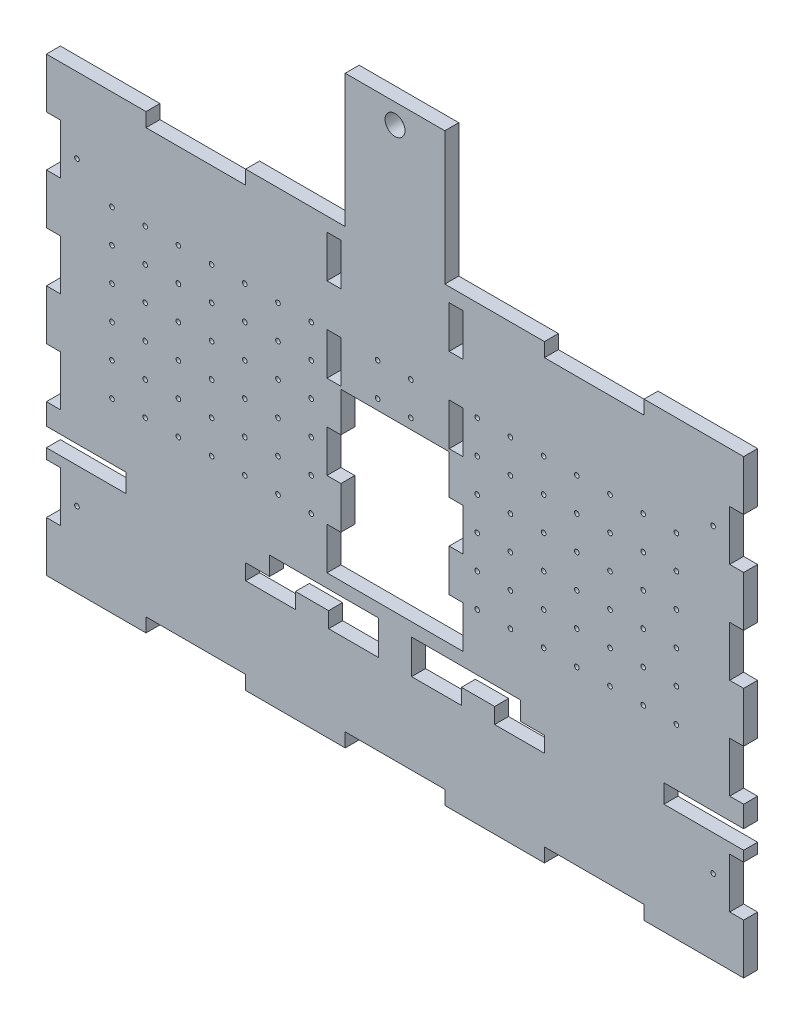
SolidWorks part; units mm, degrees
ref_plane "Front Plane" through (0, 0, 0) normal (0, 0, 1) x (1, 0, 0)
ref_plane "Top Plane" through (0, 0, 0) normal (0, 1, 0) x (1, 0, 0)
ref_plane "Right Plane" through (0, 0, 0) normal (1, 0, 0) x (0, 0, -1)
sketch "Sketch1" plane through (0, 0, 0) normal (0, 0, 1) x (1, 0, 0)
  line L1 (-127.8759, 88.4641) -> (138.8241, 88.4641)
  line L2 (-127.8759, 88.4641) -> (-127.8759, -84.2559)
  line L3 (-127.8759, -84.2559) -> (138.8241, -84.2559)
  line L4 (138.8241, 88.4641) -> (138.8241, -84.2559)
  dimension "D1" = 266.7
  dimension "D2" = 172.72
extrude "Boss-Extrude1" add sketch "Sketch1" along normal blind 5.334
sketch "Sketch2" plane through (0, 0, 5.334) normal (0, 0, 1) x (1, 0, 0)
  line L0 (-127.8759, -84.2559) -> (138.8241, -84.2559) construction
  line L1 (-89.7759, -84.2559) -> (-51.6759, -84.2559)
  line L2 (-89.7759, -84.2559) -> (-89.7759, -78.9219)
  line L3 (-89.7759, -78.9219) -> (-51.6759, -78.9219)
  line L4 (-51.6759, -84.2559) -> (-51.6759, -78.9219)
  line L5 (-89.7759, -78.9219) -> (-127.8759, -78.9219) construction
  line L6 (-13.5759, -84.2559) -> (24.5241, -84.2559)
  line L7 (-13.5759, -84.2559) -> (-13.5759, -78.9219)
  line L8 (-13.5759, -78.9219) -> (24.5241, -78.9219)
  line L9 (24.5241, -84.2559) -> (24.5241, -78.9219)
  line L10 (62.6241, -84.2559) -> (100.7241, -84.2559)
  line L11 (62.6241, -84.2559) -> (62.6241, -78.9219)
  line L12 (62.6241, -78.9219) -> (100.7241, -78.9219)
  line L13 (100.7241, -84.2559) -> (100.7241, -78.9219)
  line L14 (-127.8759, 88.4641) -> (-127.8759, -84.2559) construction
  line L15 (-51.6759, -78.9219) -> (-13.5759, -78.9219) construction
  line L16 (24.5241, -78.9219) -> (62.6241, -78.9219) construction
  line L17 (62.6241, -78.9219) -> (62.364, -79.7896) construction
  line L18 (100.7241, -78.9219) -> (138.8241, -78.9219) construction
  line L19 (138.8241, -84.2559) -> (138.8241, 88.4641) construction
  line L20 (-127.8759, 2.1041) -> (138.8241, 2.1041) construction
  line L21 (100.7241, 88.4641) -> (100.7241, 83.1301)
  line L22 (62.6241, 83.1301) -> (100.7241, 83.1301)
  line L23 (62.6241, 88.4641) -> (62.6241, 83.1301)
  line L24 (24.5241, 88.4641) -> (24.5241, 83.1301)
  line L25 (-13.5759, 83.1301) -> (24.5241, 83.1301)
  line L26 (-13.5759, 88.4641) -> (-13.5759, 83.1301)
  line L27 (-51.6759, 88.4641) -> (-51.6759, 83.1301)
  line L28 (-89.7759, 83.1301) -> (-51.6759, 83.1301)
  line L29 (-89.7759, 88.4641) -> (-89.7759, 83.1301)
  line L30 (62.6241, 88.4641) -> (100.7241, 88.4641)
  line L31 (-13.5759, 88.4641) -> (24.5241, 88.4641)
  line L32 (-89.7759, 88.4641) -> (-51.6759, 88.4641)
  dimension "D1" = 5.334
extrude "Cut-Extrude1" cut sketch "Sketch2" against normal through all
sketch "Sketch5" plane through (0, 0, 5.334) normal (0, 0, 1) x (1, 0, 0)
  line L0 (5.4741, 83.1301) -> (5.4741, -78.9219) construction
  line L1 (-13.5759, 83.1301) -> (24.5241, 83.1301) construction
  line L2 (24.5241, -78.9219) -> (-13.5759, -78.9219) construction
  line L3 (11.8241, -34.8224) -> (11.8241, -41.9344)
  line L4 (-42.5319, -34.8224) -> (-0.8759, -34.8224)
  line L5 (-42.5319, -34.8224) -> (-42.5319, -41.9344)
  line L6 (-42.5319, -41.9344) -> (-0.8759, -41.9344)
  line L7 (-0.8759, -34.8224) -> (-0.8759, -41.9344)
  line L8 (53.4801, -41.9344) -> (11.8241, -41.9344)
  line L9 (53.4801, -34.8224) -> (53.4801, -41.9344)
  line L10 (53.4801, -34.8224) -> (11.8241, -34.8224)
  line L11 (11.8241, -34.8224) -> (-0.8759, -34.8224) construction
  line L12 (-0.8759, -41.9344) -> (11.8241, -41.9344) construction
  line L13 (-139.0519, -34.8224) -> (-97.3959, -34.8224)
  line L14 (-139.0519, -34.8224) -> (-139.0519, -41.9344)
  line L15 (-139.0519, -41.9344) -> (-97.3959, -41.9344)
  line L16 (-97.3959, -34.8224) -> (-97.3959, -41.9344)
  line L18 (108.3441, -34.8224) -> (108.3441, -41.9344)
  line L19 (150.0001, -41.9344) -> (108.3441, -41.9344)
  line L20 (150.0001, -34.8224) -> (150.0001, -41.9344)
  line L21 (150.0001, -34.8224) -> (108.3441, -34.8224)
  dimension "D2" = 41.656
  dimension "D3" = 6.35
  dimension "D1" = 7.112
  dimension "D4" = 2
extrude "Cut-Extrude3" cut sketch "Sketch5" against normal through all
sketch "Sketch9" plane through (0, 0, 5.334) normal (0, 0, 1) x (1, 0, 0)
  line L0 (-127.8759, 88.4641) -> (-127.8759, -34.8224) construction
  line L1 (-127.8759, -65.0647) -> (-122.5419, -65.0647)
  line L2 (-127.8759, -65.0647) -> (-127.8759, -45.8736)
  line L3 (-127.8759, -45.8736) -> (-122.5419, -45.8736)
  line L4 (-122.5419, -65.0647) -> (-122.5419, -45.8736)
  line L5 (-122.5419, 69.273) -> (-122.5419, 88.4641) construction
  line L6 (-127.8759, -26.6825) -> (-122.5419, -26.6825)
  line L7 (-127.8759, -26.6825) -> (-127.8759, -7.4914)
  line L8 (-127.8759, -7.4914) -> (-122.5419, -7.4914)
  line L9 (-122.5419, -26.6825) -> (-122.5419, -7.4914)
  line L10 (-127.8759, 11.6997) -> (-122.5419, 11.6997)
  line L11 (-127.8759, 11.6997) -> (-127.8759, 30.8908)
  line L12 (-127.8759, 30.8908) -> (-122.5419, 30.8908)
  line L13 (-122.5419, 11.6997) -> (-122.5419, 30.8908)
  line L14 (-127.8759, 50.0819) -> (-122.5419, 50.0819)
  line L15 (-127.8759, 50.0819) -> (-127.8759, 69.273)
  line L16 (-127.8759, 69.273) -> (-122.5419, 69.273)
  line L17 (-122.5419, 50.0819) -> (-122.5419, 69.273)
  line L18 (-89.7759, 88.4641) -> (-127.8759, 88.4641) construction
  line L19 (-122.5419, 50.0819) -> (-122.5419, 30.8908) construction
  line L20 (-122.5419, 11.6997) -> (-122.5419, -7.4914) construction
  line L21 (-122.5419, -26.6825) -> (-122.5419, -45.8736) construction
  line L22 (-122.5419, -65.0647) -> (-122.5419, -84.2559) construction
  line L23 (-127.8759, -84.2559) -> (-89.7759, -84.2559) construction
  line L24 (5.4741, 83.1301) -> (5.4741, -78.9219) construction
  line L25 (-13.5759, 83.1301) -> (24.5241, 83.1301) construction
  line L26 (24.5241, -78.9219) -> (-13.5759, -78.9219) construction
  line L27 (133.4901, -65.0647) -> (133.4901, -84.2559) construction
  line L28 (133.4901, -26.6825) -> (133.4901, -45.8736) construction
  line L29 (133.4901, 11.6997) -> (133.4901, -7.4914) construction
  line L30 (133.4901, 50.0819) -> (133.4901, 30.8908) construction
  line L31 (133.4901, 69.273) -> (133.4901, 88.4641) construction
  line L32 (133.4901, 50.0819) -> (133.4901, 69.273)
  line L33 (138.8241, 69.273) -> (133.4901, 69.273)
  line L34 (138.8241, 50.0819) -> (138.8241, 69.273)
  line L35 (138.8241, 50.0819) -> (133.4901, 50.0819)
  line L36 (133.4901, 11.6997) -> (133.4901, 30.8908)
  line L37 (138.8241, 30.8908) -> (133.4901, 30.8908)
  line L38 (138.8241, 11.6997) -> (138.8241, 30.8908)
  line L39 (138.8241, 11.6997) -> (133.4901, 11.6997)
  line L40 (133.4901, -26.6825) -> (133.4901, -7.4914)
  line L41 (138.8241, -7.4914) -> (133.4901, -7.4914)
  line L42 (138.8241, -26.6825) -> (138.8241, -7.4914)
  line L43 (138.8241, -26.6825) -> (133.4901, -26.6825)
  line L44 (133.4901, -65.0647) -> (133.4901, -45.8736)
  line L45 (138.8241, -45.8736) -> (133.4901, -45.8736)
  line L46 (138.8241, -65.0647) -> (138.8241, -45.8736)
  line L47 (138.8241, -65.0647) -> (133.4901, -65.0647)
  dimension "D1" = 5.334
extrude "Cut-Extrude7" cut sketch "Sketch9" against normal through all
sketch "Sketch10" plane through (0, 88.4641, 0) normal (0, 1, 0) x (1, 0, 0)
  line L1 (24.5241, -5.334) -> (62.6241, -5.334)
  line L2 (24.5241, -5.334) -> (24.5241, 0)
  line L3 (24.5241, 0) -> (62.6241, 0)
  line L4 (62.6241, -5.334) -> (62.6241, 0)
extrude "Boss-Extrude2" add sketch "Sketch10" along normal blind 50.8
sketch "Sketch11" plane through (0, 0, 0) normal (0, 0, -1) x (-1, 0, 0)
  line L0 (-24.5241, 83.1301) -> (-24.5241, 139.2641) construction
  line L1 (-24.5241, 88.4641) -> (-31.1281, 88.4641)
  line L2 (-24.5241, 88.4641) -> (-24.5241, 129.1041)
  line L3 (-24.5241, 129.1041) -> (-31.1281, 129.1041)
  line L4 (-31.1281, 88.4641) -> (-31.1281, 129.1041)
  line L5 (13.5759, 88.4641) -> (51.6759, 88.4641) construction
  dimension "D1" = 6.604
  dimension "D3" = 0
extrude "Cut-Extrude8" cut sketch "Sketch11" against normal through all
sketch "Sketch12" plane through (0, 0, 5.334) normal (0, 0, 1) x (1, 0, 0)
  line L0 (62.6241, 139.2641) -> (62.6241, 83.1301) construction
  circle A0 centre (43.5741, 130.4765) radius 3.81
  dimension "D1" = 19.05
extrude "Cut-Extrude9" cut sketch "Sketch12" against normal through all
sketch "Sketch14" plane through (0, 0, 5.334) normal (0, 0, 1) x (1, 0, 0)
  line L0 (-89.7759, 88.4641) -> (-127.8759, 88.4641) construction
  circle A0 centre (-102.7976, 50.3641) radius 0.889
  circle A1 centre (-90.0976, 50.3641) radius 0.889
  circle A2 centre (-77.3976, 50.3641) radius 0.889
  circle A3 centre (-64.6976, 50.3641) radius 0.889
  circle A4 centre (-51.9976, 50.3641) radius 0.889
  circle A5 centre (-39.2976, 50.3641) radius 0.889
  circle A6 centre (-26.5976, 50.3641) radius 0.889
  circle A8 centre (-1.1976, 50.3641) radius 0.889
  circle A9 centre (11.5024, 50.3641) radius 0.889
  circle A11 centre (36.9024, 50.3641) radius 0.889
  circle A12 centre (49.6024, 50.3641) radius 0.889
  circle A13 centre (62.3024, 50.3641) radius 0.889
  circle A14 centre (75.0024, 50.3641) radius 0.889
  circle A15 centre (87.7024, 50.3641) radius 0.889
  circle A16 centre (100.4024, 50.3641) radius 0.889
  circle A17 centre (113.1024, 50.3641) radius 0.889
  circle A18 centre (-102.7976, 37.6641) radius 0.889
  circle A19 centre (-90.0976, 37.6641) radius 0.889
  circle A20 centre (-77.3976, 37.6641) radius 0.889
  circle A21 centre (-64.6976, 37.6641) radius 0.889
  circle A22 centre (-51.9976, 37.6641) radius 0.889
  circle A23 centre (-39.2976, 37.6641) radius 0.889
  circle A24 centre (-26.5976, 37.6641) radius 0.889
  circle A26 centre (-1.1976, 37.6641) radius 0.889
  circle A27 centre (11.5024, 37.6641) radius 0.889
  circle A29 centre (36.9024, 37.6641) radius 0.889
  circle A30 centre (49.6024, 37.6641) radius 0.889
  circle A31 centre (62.3024, 37.6641) radius 0.889
  circle A32 centre (75.0024, 37.6641) radius 0.889
  circle A33 centre (87.7024, 37.6641) radius 0.889
  circle A34 centre (100.4024, 37.6641) radius 0.889
  circle A35 centre (113.1024, 37.6641) radius 0.889
  circle A36 centre (-102.7976, 24.9641) radius 0.889
  circle A37 centre (-90.0976, 24.9641) radius 0.889
  circle A38 centre (-77.3976, 24.9641) radius 0.889
  circle A39 centre (-64.6976, 24.9641) radius 0.889
  circle A40 centre (-51.9976, 24.9641) radius 0.889
  circle A41 centre (-39.2976, 24.9641) radius 0.889
  circle A42 centre (-26.5976, 24.9641) radius 0.889
  circle A44 centre (-1.1976, 24.9641) radius 0.889
  circle A45 centre (11.5024, 24.9641) radius 0.889
  circle A47 centre (36.9024, 24.9641) radius 0.889
  circle A48 centre (49.6024, 24.9641) radius 0.889
  circle A49 centre (62.3024, 24.9641) radius 0.889
  circle A50 centre (75.0024, 24.9641) radius 0.889
  circle A51 centre (87.7024, 24.9641) radius 0.889
  circle A52 centre (100.4024, 24.9641) radius 0.889
  circle A53 centre (113.1024, 24.9641) radius 0.889
  circle A54 centre (-102.7976, 12.2641) radius 0.889
  circle A55 centre (-90.0976, 12.2641) radius 0.889
  circle A56 centre (-77.3976, 12.2641) radius 0.889
  circle A57 centre (-64.6976, 12.2641) radius 0.889
  circle A58 centre (-51.9976, 12.2641) radius 0.889
  circle A59 centre (-39.2976, 12.2641) radius 0.889
  circle A60 centre (-26.5976, 12.2641) radius 0.889
  circle A65 centre (36.9024, 12.2641) radius 0.889
  circle A66 centre (49.6024, 12.2641) radius 0.889
  circle A67 centre (62.3024, 12.2641) radius 0.889
  circle A68 centre (75.0024, 12.2641) radius 0.889
  circle A69 centre (87.7024, 12.2641) radius 0.889
  circle A70 centre (100.4024, 12.2641) radius 0.889
  circle A71 centre (113.1024, 12.2641) radius 0.889
  circle A72 centre (-102.7976, -0.4359) radius 0.889
  circle A73 centre (-90.0976, -0.4359) radius 0.889
  circle A74 centre (-77.3976, -0.4359) radius 0.889
  circle A75 centre (-64.6976, -0.4359) radius 0.889
  circle A76 centre (-51.9976, -0.4359) radius 0.889
  circle A77 centre (-39.2976, -0.4359) radius 0.889
  circle A78 centre (-26.5976, -0.4359) radius 0.889
  circle A79 centre (-13.8976, -0.4359) radius 0.889
  circle A80 centre (-1.1976, -0.4359) radius 0.889
  circle A81 centre (11.5024, -0.4359) radius 0.889
  circle A82 centre (24.2024, -0.4359) radius 0.889
  circle A83 centre (36.9024, -0.4359) radius 0.889
  circle A84 centre (49.6024, -0.4359) radius 0.889
  circle A85 centre (62.3024, -0.4359) radius 0.889
  circle A86 centre (75.0024, -0.4359) radius 0.889
  circle A87 centre (87.7024, -0.4359) radius 0.889
  circle A88 centre (100.4024, -0.4359) radius 0.889
  circle A89 centre (113.1024, -0.4359) radius 0.889
  circle A90 centre (-102.7976, -13.1359) radius 0.889
  circle A91 centre (-90.0976, -13.1359) radius 0.889
  circle A92 centre (-77.3976, -13.1359) radius 0.889
  circle A93 centre (-64.6976, -13.1359) radius 0.889
  circle A94 centre (-51.9976, -13.1359) radius 0.889
  circle A95 centre (-39.2976, -13.1359) radius 0.889
  circle A96 centre (-26.5976, -13.1359) radius 0.889
  circle A97 centre (-13.8976, -13.1359) radius 0.889
  circle A98 centre (-1.1976, -13.1359) radius 0.889
  circle A99 centre (11.5024, -13.1359) radius 0.889
  circle A100 centre (24.2024, -13.1359) radius 0.889
  circle A101 centre (36.9024, -13.1359) radius 0.889
  circle A102 centre (49.6024, -13.1359) radius 0.889
  circle A103 centre (62.3024, -13.1359) radius 0.889
  circle A104 centre (75.0024, -13.1359) radius 0.889
  circle A105 centre (87.7024, -13.1359) radius 0.889
  circle A106 centre (100.4024, -13.1359) radius 0.889
  circle A107 centre (113.1024, -13.1359) radius 0.889
  circle A108 centre (-1.1976, 12.2641) radius 0.889 [skipped]
  circle A110 centre (11.5024, 12.2641) radius 0.889 [skipped]
  circle A116 centre (24.2024, 50.3641) radius 0.889 [skipped]
  circle A117 centre (-13.8976, 50.3641) radius 0.889 [skipped]
  dimension "D1" = 18
  dimension "D2" = 38.1
  dimension "D4" = 1.778
  dimension "D3" = 6
extrude "Cut-Extrude11" cut sketch "Sketch14" against normal through all
sketch "Sketch15" plane through (0, 0, 5.334) normal (0, 0, 1) x (1, 0, 0)
  line L1 (31.1281, 129.1041) -> (24.5241, 129.1041)
  line L2 (31.1281, 129.1041) -> (31.1281, 139.2641)
  line L3 (31.1281, 139.2641) -> (24.5241, 139.2641)
  line L4 (24.5241, 129.1041) -> (24.5241, 139.2641)
extrude "Cut-Extrude12" cut sketch "Sketch15" against normal through all
sketch "Sketch16" plane through (0, 0, 5.334) normal (0, 0, 1) x (1, 0, 0)
  line L0 (5.4741, 83.1301) -> (5.4741, -78.9219) construction
  line L1 (-15.2269, 33.7576) -> (26.1751, 33.7576)
  line L2 (-15.2269, 33.7576) -> (-15.2269, -29.7424)
  line L3 (-15.2269, -29.7424) -> (26.1751, -29.7424)
  line L4 (26.1751, 33.7576) -> (26.1751, -29.7424)
  line L5 (-13.5759, 83.1301) -> (24.5241, 83.1301) construction
  line L6 (24.5241, -78.9219) -> (-13.5759, -78.9219) construction
  line L8 (-0.8759, -34.8224) -> (-42.5319, -34.8224) construction
  dimension "D1" = 63.5
  dimension "D2" = 41.402
  dimension "D3" = 20.701
  dimension "D4" = 5.08
extrude "Cut-Extrude13" cut sketch "Sketch16" against normal through all
sketch "Sketch17" plane through (0, 0, 5.334) normal (0, 0, 1) x (1, 0, 0)
  line L0 (-15.2269, 33.7576) -> (-15.2269, -29.7424) construction
  line L1 (-15.2269, -29.7424) -> (-20.5609, -29.7424)
  line L2 (-15.2269, -29.7424) -> (-15.2269, -13.6178)
  line L3 (-15.2269, -13.6178) -> (-20.5609, -13.6178)
  line L4 (-20.5609, -29.7424) -> (-20.5609, -13.6178)
  line L5 (-15.2269, 2.5069) -> (-20.5609, 2.5069)
  line L6 (-15.2269, 2.5069) -> (-15.2269, 18.6315)
  line L7 (-15.2269, 18.6315) -> (-20.5609, 18.6315)
  line L8 (-20.5609, 2.5069) -> (-20.5609, 18.6315)
  line L9 (-20.5609, -13.6178) -> (-20.5609, 2.5069) construction
  line L10 (-20.5609, 50.8808) -> (-15.2269, 50.8808)
  line L11 (-20.5609, 50.8808) -> (-20.5609, 34.7562)
  line L12 (-20.5609, 34.7562) -> (-15.2269, 34.7562)
  line L13 (-15.2269, 50.8808) -> (-15.2269, 34.7562)
  line L14 (-20.5609, 67.0055) -> (-15.2269, 67.0055)
  line L15 (-20.5609, 67.0055) -> (-20.5609, 83.1301)
  line L16 (-20.5609, 83.1301) -> (-15.2269, 83.1301)
  line L17 (-15.2269, 67.0055) -> (-15.2269, 83.1301)
  line L18 (-20.5609, 18.6315) -> (-20.5609, 34.7562) construction
  line L19 (-20.5609, 67.0055) -> (-20.5609, 50.8808) construction
  line L20 (5.4741, 83.1301) -> (5.4741, -78.9219) construction
  line L21 (-13.5759, 83.1301) -> (24.5241, 83.1301) construction
  line L22 (24.5241, -78.9219) -> (-13.5759, -78.9219) construction
  line L23 (31.5091, 67.0055) -> (31.5091, 50.8808) construction
  line L24 (31.5091, 18.6315) -> (31.5091, 34.7562) construction
  line L25 (31.5091, -13.6178) -> (31.5091, 2.5069) construction
  line L26 (26.1751, 67.0055) -> (26.1751, 83.1301)
  line L27 (31.5091, 83.1301) -> (26.1751, 83.1301)
  line L28 (31.5091, 67.0055) -> (31.5091, 83.1301)
  line L29 (31.5091, 67.0055) -> (26.1751, 67.0055)
  line L30 (26.1751, 50.8808) -> (26.1751, 34.7562)
  line L31 (31.5091, 34.7562) -> (26.1751, 34.7562)
  line L32 (31.5091, 50.8808) -> (31.5091, 34.7562)
  line L33 (31.5091, 50.8808) -> (26.1751, 50.8808)
  line L34 (31.5091, 2.5069) -> (31.5091, 18.6315)
  line L35 (26.1751, 18.6315) -> (31.5091, 18.6315)
  line L36 (26.1751, 2.5069) -> (26.1751, 18.6315)
  line L37 (26.1751, 2.5069) -> (31.5091, 2.5069)
  line L38 (31.5091, -29.7424) -> (31.5091, -13.6178)
  line L39 (26.1751, -13.6178) -> (31.5091, -13.6178)
  line L40 (26.1751, -29.7424) -> (26.1751, -13.6178)
  line L41 (26.1751, -29.7424) -> (31.5091, -29.7424)
  dimension "D1" = 0
  dimension "D2" = 5.334
  dimension "D3" = 5.334
  dimension "D4" = 5.334
extrude "Cut-Extrude14" cut sketch "Sketch17" against normal through all
sketch "Sketch18" plane through (0, 0, 5.334) normal (0, 0, 1) x (1, 0, 0)
  line L0 (24.5241, 83.1301) -> (24.5241, 148.9274) construction
  line L1 (31.1281, 139.2641) -> (62.6241, 139.2641) construction
  line L2 (-13.5759, 83.1301) -> (24.5241, 83.1301)
  line L3 (-13.5759, 83.1301) -> (-13.5759, 139.2641)
  line L4 (-13.5759, 139.2641) -> (24.5241, 139.2641)
  line L5 (24.5241, 83.1301) -> (24.5241, 139.2641)
  dimension "D1" = 0
extrude "Boss-Extrude3" add sketch "Sketch18" against normal blind 5.334
sketch "Sketch19" plane through (0, 0, 5.334) normal (0, 0, 1) x (1, 0, 0)
  line L1 (31.1281, 88.4641) -> (65.8849, 88.4641)
  line L2 (31.1281, 88.4641) -> (31.1281, 143.4078)
  line L3 (31.1281, 143.4078) -> (65.8849, 143.4078)
  line L4 (65.8849, 88.4641) -> (65.8849, 143.4078)
extrude "Cut-Extrude15" cut sketch "Sketch19" against normal through all
sketch "Sketch20" plane through (0, 0, 5.334) normal (0, 0, 1) x (1, 0, 0)
  line L0 (5.4741, 139.2641) -> (5.4741, 29.9476) construction
  line L1 (24.5241, 139.2641) -> (-13.5759, 139.2641) construction
  circle A0 centre (5.4741, 131.6441) radius 3.81
  dimension "D1" = 7.62
  dimension "D3" = 7.62
  dimension "D2" = 0
extrude "Cut-Extrude16" cut sketch "Sketch20" against normal through all contours A0
sketch "Sketch21" plane through (0, 0, 5.334) normal (0, 0, 1) x (1, 0, 0)
  line L0 (133.4901, 59.6775) -> (-122.5419, 59.6775) construction
  line L1 (133.4901, 69.273) -> (133.4901, 50.0819) construction
  line L2 (-122.5419, 50.0819) -> (-122.5419, 69.273) construction
  line L3 (-122.5419, -55.4692) -> (133.4901, -55.4692) construction
  line L4 (-122.5419, -65.0647) -> (-122.5419, -45.8736) construction
  line L5 (133.4901, -45.8736) -> (133.4901, -65.0647) construction
  line L6 (138.8241, 2.1041) -> (-127.8759, 2.1041) construction
  line L7 (138.8241, -7.4914) -> (138.8241, 11.6997) construction
  line L8 (-127.8759, 11.6997) -> (-127.8759, -7.4914) construction
  line L9 (5.4741, 139.2641) -> (5.4741, -78.9219) construction
  line L10 (24.5241, 139.2641) -> (-13.5759, 139.2641) construction
  line L11 (24.5241, -78.9219) -> (-13.5759, -78.9219) construction
  circle A0 centre (127.1401, 59.6775) radius 0.889
  circle A1 centre (-116.1919, 59.6775) radius 0.889
  circle A2 centre (-116.1919, -55.4692) radius 0.889
  circle A3 centre (127.1401, -55.4692) radius 0.889
  dimension "D1" = 1.778
  dimension "D2" = 0
  dimension "D3" = 6.35
extrude "Cut-Extrude17" cut sketch "Sketch21" against normal through all
sketch "Sketch22" plane through (0, 0, 0) normal (0, 0, -1) x (-1, 0, 0)
  line L0 (-11.8241, -41.9344) -> (-53.4801, -41.9344) construction
  line L1 (-30.8741, -41.9344) -> (-11.8241, -41.9344)
  line L2 (-30.8741, -41.9344) -> (-30.8741, -47.9281)
  line L3 (-30.8741, -47.9281) -> (-11.8241, -47.9281)
  line L4 (-11.8241, -41.9344) -> (-11.8241, -47.9281)
  line L5 (-11.8241, -34.8224) -> (-11.8241, -41.9344) construction
  line L6 (-62.6241, -47.9281) -> (-43.5741, -47.9281)
  line L7 (-43.5741, -41.9344) -> (-43.5741, -47.9281)
  line L8 (-62.6241, -41.9344) -> (-43.5741, -41.9344)
  line L9 (-62.6241, -41.9344) -> (-62.6241, -47.9281)
  line L10 (-5.4741, -78.9219) -> (-5.4741, 95.0308) construction
  line L11 (-24.5241, -78.9219) -> (13.5759, -78.9219) construction
  line L12 (51.6759, -41.9344) -> (51.6759, -47.9281)
  line L13 (51.6759, -41.9344) -> (32.6259, -41.9344)
  line L14 (32.6259, -41.9344) -> (32.6259, -47.9281)
  line L15 (51.6759, -47.9281) -> (32.6259, -47.9281)
  line L16 (0.8759, -41.9344) -> (0.8759, -47.9281)
  line L17 (19.9259, -47.9281) -> (0.8759, -47.9281)
  line L18 (19.9259, -41.9344) -> (19.9259, -47.9281)
  line L19 (19.9259, -41.9344) -> (0.8759, -41.9344)
  dimension "D1" = 19.05
  dimension "D2" = 0
  dimension "D3" = 2
extrude "Cut-Extrude18" cut sketch "Sketch22" against normal through all
equation "\"MDF\"= .21in"
equation "\"Foamcore\"= .13in"
equation "\"Gmaterial\"= \"MDF\""
equation "\"D1@Boss-Extrude1\"=\"MDF\""
equation "\"D1@Sketch2\"=\"MDF\""
equation "\"D1@Sketch5\"=\"MDF\"+0.07"
equation "\"D1@Sketch9\"=\"MDF\""
equation "\"D1@Sketch11\"=\"MDF\"+.05"
equation "\"D2@Sketch17\"=\"MDF\""
equation "\"D3@Sketch17\"=\"MDF\""
equation "\"D4@Sketch17\"=\"MDF\""
equation "\"D1@Boss-Extrude3\"=\"MDF\""
